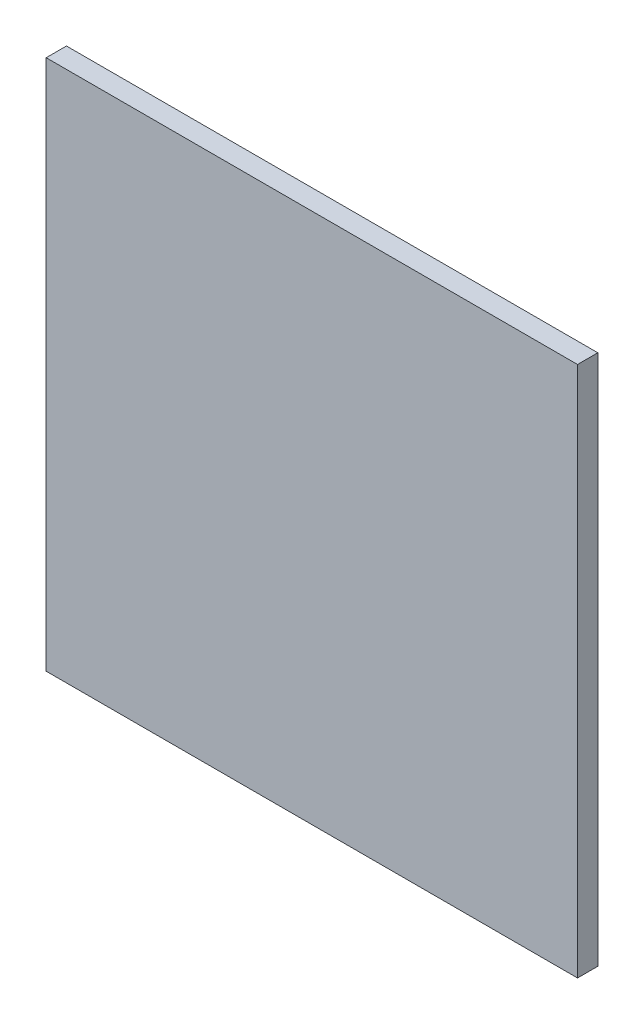
SolidWorks part; units mm, degrees
ref_plane "Ebene vorne" through (0, 0, 0) normal (0, 0, 1) x (1, 0, 0)
ref_plane "Ebene oben" through (0, 0, 0) normal (0, 1, 0) x (1, 0, 0)
ref_plane "Ebene rechts" through (0, 0, 0) normal (1, 0, 0) x (0, 0, -1)
sketch "Skizze2" plane through (0, 0, 0) normal (0, 0, 1) x (1, 0, 0)
  line L0 (-65.5, 65.5) -> (-65.5, -65.5) construction
  line L1 (-65.5, -65.5) -> (65.5, -65.5) construction
  line L2 (65.5, 65.5) -> (-65.5, 65.5) construction
  line L3 (65.5, -65.5) -> (65.5, 65.5) construction
  line L4 (-65.5, 65.5) -> (-65.5, -65.5)
  line L5 (-65.5, -65.5) -> (65.5, -65.5)
  line L6 (65.5, 65.5) -> (-65.5, 65.5)
  line L7 (65.5, -65.5) -> (65.5, 65.5)
extrude "Aufsatz-Linear austragen1" add sketch "Skizze2" along normal blind 5
